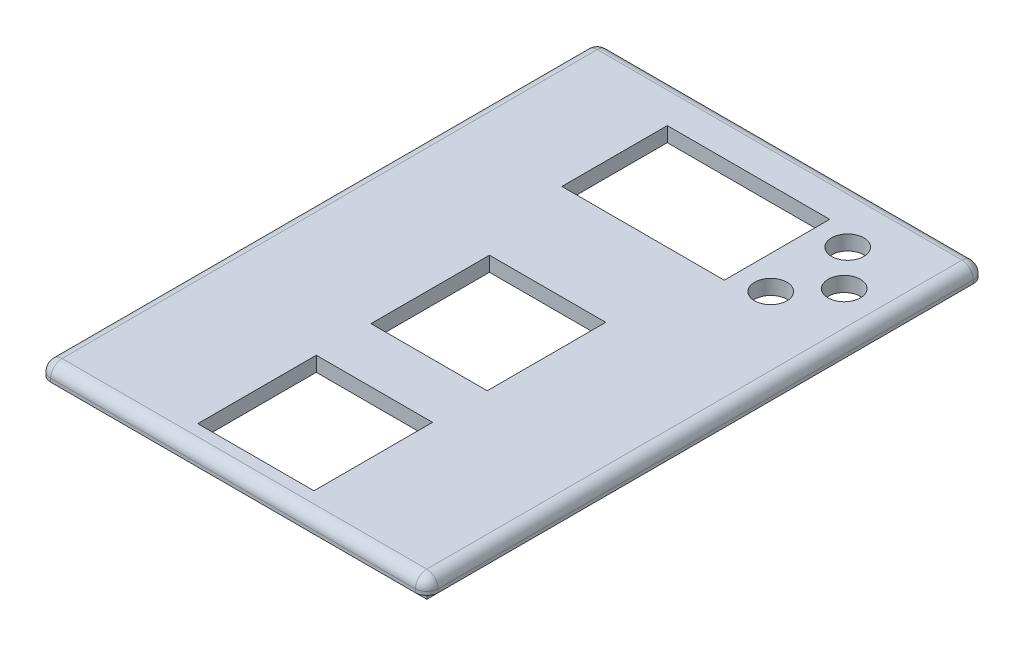
SolidWorks part; units mm, degrees
material "ABS"
ref_plane "Front Plane" through (0, 0, 0) normal (0, 0, 1) x (1, 0, 0)
ref_plane "Top Plane" through (0, 0, 0) normal (0, 1, 0) x (1, 0, 0)
ref_plane "Right Plane" through (0, 0, 0) normal (1, 0, 0) x (0, 0, -1)
sketch "Sketch1" plane through (0, 0, 0) normal (0, 1, 0) x (1, 0, 0)
  line L1 (0, 0) -> (86.36, 0)
  line L2 (0, 0) -> (0, 124.333)
  line L3 (0, 124.333) -> (86.36, 124.333)
  line L4 (86.36, 0) -> (86.36, 124.333)
extrude "Boss-Extrude1" add sketch "Sketch1" along normal blind 3.302
sketch "Sketch2" plane through (0, 0, 0) normal (0, -1, 0) x (1, 0, 0)
  line L1 (2.54, -2.54) -> (83.82, -2.54)
  line L2 (2.54, -2.54) -> (2.54, -121.793)
  line L3 (2.54, -121.793) -> (83.82, -121.793)
  line L4 (83.82, -2.54) -> (83.82, -121.793)
extrude "Boss-Extrude2" add sketch "Sketch2" along normal blind 2.54
sketch "Sketch4" plane through (0, -2.54, 0) normal (0, -1, 0) x (1, 0, 0)
  line L2 (2.54, -121.793) -> (83.82, -121.793) construction
  line L3 (63.5, -121.793) -> (63.5, -119.253)
  line L4 (81.28, -119.253) -> (81.28, -5.08)
  line L5 (63.5, -119.253) -> (81.28, -119.253)
  line L6 (5.08, -119.253) -> (5.08, -5.08)
  line L7 (22.86, -121.793) -> (63.5, -121.793)
  line L8 (81.28, -5.08) -> (63.5, -5.08)
  line L9 (22.86, -2.54) -> (63.5, -2.54)
  line L10 (63.5, -5.08) -> (63.5, -2.54)
  line L11 (83.82, -2.54) -> (2.54, -2.54) construction
  line L12 (22.86, -2.54) -> (22.86, -5.08)
  line L13 (22.86, -5.08) -> (5.08, -5.08)
  line L14 (5.08, -119.253) -> (22.86, -119.253)
  line L15 (22.86, -119.253) -> (22.86, -121.793)
extrude "Cut-Extrude1" cut sketch "Sketch4" against normal blind 2.54
sketch "Sketch6" plane through (0, 3.302, 0) normal (0, 1, 0) x (1, 0, 0)
  line L1 (30.226, 5.08) -> (56.134, 5.08)
  line L2 (30.226, 5.08) -> (30.226, 31.496)
  line L3 (30.226, 31.496) -> (56.134, 31.496)
  line L4 (56.134, 5.08) -> (56.134, 31.496)
  line L5 (30.226, 43.688) -> (56.134, 43.688)
  line L6 (30.226, 43.688) -> (30.226, 70.104)
  line L7 (30.226, 70.104) -> (56.134, 70.104)
  line L8 (56.134, 43.688) -> (56.134, 70.104)
  line L9 (25.019, 114.935) -> (61.214, 114.935)
  line L10 (25.019, 114.935) -> (25.019, 91.44)
  line L11 (25.019, 91.44) -> (61.214, 91.44)
  line L12 (61.214, 114.935) -> (61.214, 91.44)
extrude "Cut-Extrude2" cut sketch "Sketch6" against normal blind 3.302
fillet "Fillet1" radius 2.54 8 edges at (86.36, 3.302, -62.1665) (43.18, 3.302, 0) (43.18, 3.302, -124.333) (0, 3.302, -62.1665) (0, 1.651, -124.333) (0, 1.651, 0) (86.36, 1.651, 0) (86.36, 1.651, -124.333)
sketch "Sketch7" plane through (0, 3.302, 0) normal (0, 1, 0) x (1, 0, 0)
  circle A0 centre (68.58, 111.5789) radius 3.6
  circle A1 centre (76.2, 103.1875) radius 3.6
  circle A2 centre (68.58, 94.4339) radius 3.6
extrude "Cut-Extrude3" cut sketch "Sketch7" against normal through all
